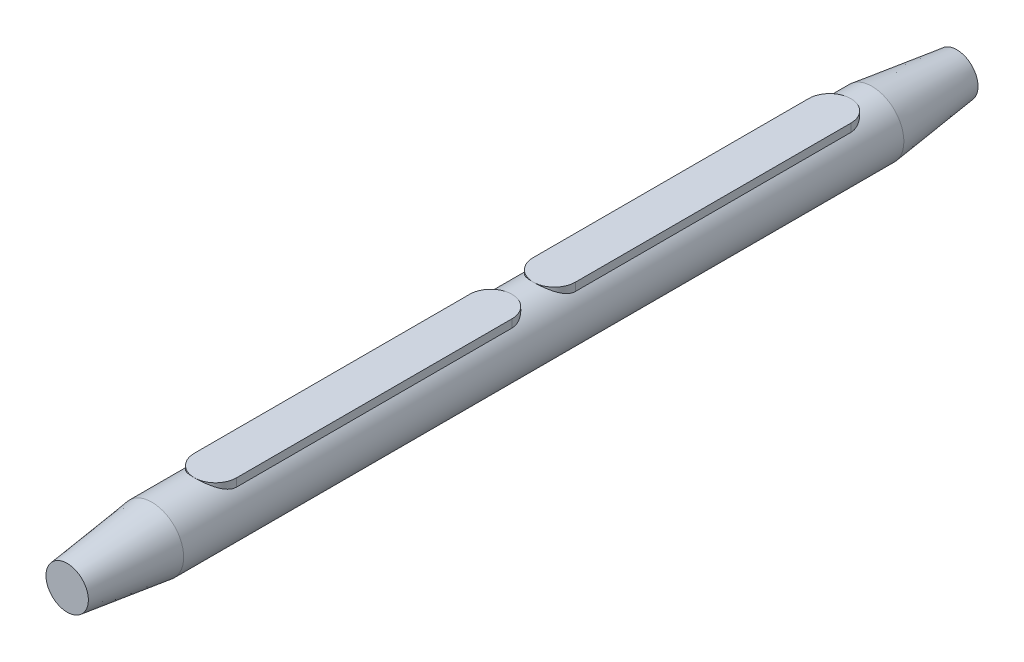
SolidWorks part; units mm, degrees
ref_plane "Front Plane" through (0, 0, 0) normal (0, 0, 1) x (1, 0, 0)
ref_plane "Top Plane" through (0, 0, 0) normal (0, 1, 0) x (1, 0, 0)
ref_plane "Right Plane" through (0, 0, 0) normal (1, 0, 0) x (0, 0, -1)
sketch "Section" plane through (0, 0, 0) normal (0, 0, 1) x (1, 0, 0)
  circle A0 centre (0, 0) radius 150
  dimension "D1" = 300
extrude "Boss-Extrude1" add sketch "Section" along normal blind 3400 contours A0
sketch "ConoProa" plane through (0, 0, 0) normal (1, 0, 0) x (0, 0, -1)
  line L4 (-3400, 0) -> (-3800, 0) construction
  line L5 (-3400, 150) -> (-3400, -150) construction
  line L6 (-3800, 0) -> (-3800, 100)
  line L7 (-3800, 100) -> (-3400, 150)
  line L8 (-3400, 150) -> (-3400, 0)
  line L9 (-3400, 0) -> (-3800, 0)
  dimension "D1" = 100
  dimension "D2" = 400
sketch "ConoPopa" plane through (0, 0, 0) normal (1, 0, 0) x (0, 0, -1)
  line L0 (0, 0) -> (400, 0) construction
  line L1 (0, -150) -> (0, 150) construction
  line L2 (400, 0) -> (400, 100)
  line L3 (400, 100) -> (0, 150)
  line L4 (0, 150) -> (0, 0)
  line L5 (0, 0) -> (400, 0)
  dimension "D1" = 400
  dimension "D2" = 100
revolve "Revolve1" add sketch "ConoPopa" angle 360 about L0
revolve "Revolve2" add sketch "ConoProa" angle 360 about L4
ref_axis "Axis1" through (0, 0, 3400) along (0, 0, -1)
ref_plane "TopSupportTangentPlane" through (0, 150, 0) normal (0, 1, 0) x (1, 0, 0)
sketch "Sketch1" plane through (0, 150, 0) normal (0, 1, 0) x (1, 0, 0)
  line L0 (0, 0) -> (0, -3399.159) construction
  line L1 (0, -3400) -> (0, 0) construction
  line L2 (0, -200) -> (0, -1500) construction
  line L3 (-100, -1500) -> (-100, -200)
  line L4 (100, -1500) -> (100, -200)
  line L5 (-571.7501, -1650) -> (574.9852, -1650) construction
  line L6 (-100, -1800) -> (-100, -3100)
  line L7 (100, -1800) -> (100, -3100)
  line L9 (0, -200) -> (0, -100) construction
  arc A0 (100, -200) -> (-100, -200) centre (0, -200) ccw
  arc A1 (-100, -1500) -> (100, -1500) centre (0, -1500) ccw
  arc A2 (-100, -1800) -> (100, -1800) centre (0, -1800) cw
  arc A3 (100, -3100) -> (-100, -3100) centre (0, -3100) cw
  dimension "D1" = 200
  dimension "D4" = 150
  dimension "D2" = 200
  dimension "D3" = 1300
extrude "Boss-Extrude2" add sketch "Sketch1" against normal up to surface up to face at (150, 0, 3400)
